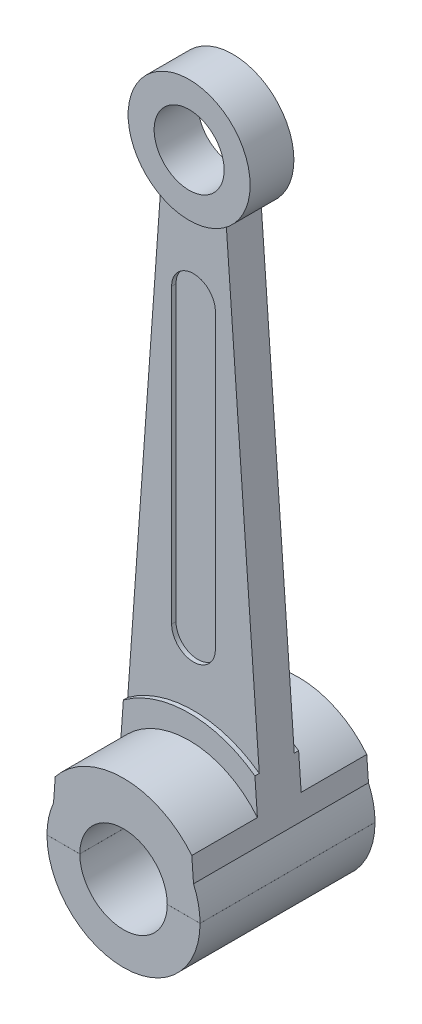
SolidWorks part; units mm, degrees
note: The reader was unsure of these and kept them because the rebuilt part matched: shared geometry of "Sketch1<3>", "Sketch1<4>".
ref_plane "Front Plane" through (0, 0, 0) normal (0, 0, 1) x (1, 0, 0)
ref_plane "Top Plane" through (0, 0, 0) normal (0, 1, 0) x (1, 0, 0)
ref_plane "Right Plane" through (0, 0, 0) normal (1, 0, 0) x (0, 0, -1)
sketch "Sketch1" plane through (0, 0, 0) normal (0, 0, 1) x (1, 0, 0)
  line L0 (0, 13.69) -> (0, -1) construction
  line L1 (-1.65, 1.9311) -> (-0.75, 12.5138)
  line L2 (1.65, 1.9311) -> (0.75, 12.5138)
  line L3 (0, 4) -> (0, 10.69) construction
  line L4 (-0.5, 4) -> (-0.5, 10.69)
  line L5 (0.5, 4) -> (0.5, 10.69)
  circle A0 centre (0, 0) radius 2.54
  circle A1 centre (0, 0) radius 1
  circle A2 centre (0, 13.69) radius 1.395
  circle A3 centre (0, 13.69) radius 0.8
  arc A4 (-0.5, 4) -> (0.5, 4) centre (0, 4) ccw
  arc A5 (0.5, 10.69) -> (-0.5, 10.69) centre (0, 10.69) ccw
  point P14 (0, 7.345)
  dimension "D1" = 1.6
  dimension "D2" = 2.79
  dimension "D3" = 5.08
  dimension "D4" = 2
  dimension "D7" = 0.5
  dimension "D5" = 13.69
  dimension "D6" = 1.5
  dimension "D8" = 3
  dimension "D9" = 4
  dimension "D10" = 3.3
extrude "Boss-Extrude1" add sketch "Sketch1" along normal mid plane 1 contours A2 A3 | A0 A1
extrude "Boss-Extrude2" add sketch "Sketch1<3>" along normal mid plane 0.8 contours A2 L1 A0 L2 A5 L5 A4 L4
sketch "Sketch1<3>" plane through (0, 0, 0) normal (0, 0, 1) x (1, 0, 0) same geometry as "Sketch1"
extrude "Boss-Extrude3" add sketch "Sketch1<4>" along normal mid plane 0.6 contours L4 A5 L5 A4
sketch "Sketch1<4>" plane through (0, 0, 0) normal (0, 0, 1) x (1, 0, 0) same geometry as "Sketch1"
sketch "Sketch2" plane through (0, 0, 0.5) normal (0, 0, 1) x (1, 0, 0)
  circle A0 centre (0, 0) radius 2
  circle A1 centre (0, 0) radius 1
  circle A2 centre (0, 0) radius 1 construction
  dimension "D1" = 4
  dimension "D2" = 2
extrude "Boss-Extrude4" add sketch "Sketch2" along normal blind 1.5 and the other way blind 2.5 contours A0
sketch "Sketch3" plane through (0, 0, 0) normal (0, 0, 1) x (1, 0, 0)
  line L0 (-0.75, 12.5138) -> (-2.8936, 1.969)
  line L1 (0.75, 12.5138) -> (2.8936, 1.969)
  line L2 (-0.75, 12.5138) -> (-1.6, 0.7089)
  line L3 (1.6, 0.7089) -> (0.75, 12.5138)
  arc A0 (-2.8936, 1.969) -> (2.8936, 1.969) centre (0, 0) ccw
  arc A1 (-1.6, 0.7089) -> (1.6, 0.7089) centre (0, 0) ccw
  dimension "D2" = 1.75
  dimension "D3" = 3.5
  dimension "D1" = 3.2
extrude "Cut-Extrude1" cut sketch "Sketch3" against normal mid plane 41.5
sketch "Sketch4" plane through (0, 0, 0) normal (0, 0, 1) x (1, 0, 0)
  line L0 (-2.4867, 0) -> (4.9534, 0) construction
  line L2 (2.5867, 0) -> (-2.8403, 0)
  line L3 (2.5867, 0) -> (2.5867, 0.001)
  line L4 (2.5867, 0.001) -> (-2.8403, 0.001)
  line L5 (-2.8403, 0) -> (-2.8403, 0.001)
  dimension "D1" = 0.001
extrude "Cut-Extrude2" cut sketch "Sketch4" against normal mid plane 41.5
